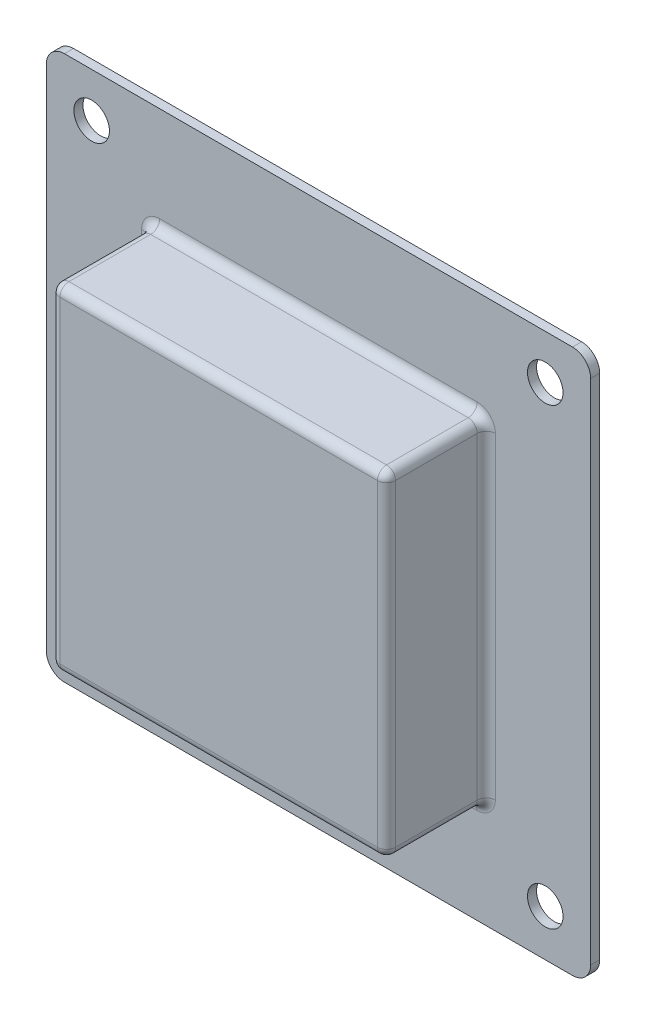
SolidWorks part; units mm, degrees
material "ABS PC"
ref_plane "Front Plane" through (0, 0, 0) normal (0, 0, 1) x (1, 0, 0)
ref_plane "Top Plane" through (0, 0, 0) normal (0, 1, 0) x (1, 0, 0)
ref_plane "Right Plane" through (0, 0, 0) normal (1, 0, 0) x (0, 0, -1)
sketch "Sketch1" plane through (0, 0, 0) normal (0, 0, 1) x (1, 0, 0)
  line L0 (34.9305, 50.2951) -> (34.9305, 88.3951)
  line L1 (34.9305, 85.8551) -> (34.9305, 14.7351) construction
  line L6 (34.9305, 88.3951) -> (-41.2695, 88.3951)
  line L7 (-41.2695, 88.3951) -> (-41.2695, 12.1951)
  line L8 (-41.2695, 12.1951) -> (34.9305, 12.1951)
  line L9 (34.9305, 12.1951) -> (34.9305, 50.2951)
  line L10 (34.9305, 50.2951) -> (19.0555, 50.2951) construction
  line L11 (19.0555, 50.2951) -> (19.0555, 72.5201)
  line L12 (19.0555, 72.5201) -> (-25.3945, 72.5201)
  line L13 (-25.3945, 72.5201) -> (-25.3945, 28.0701)
  line L14 (-25.3945, 28.0701) -> (19.0555, 28.0701)
  line L15 (19.0555, 28.0701) -> (19.0555, 50.2951)
extrude "Boss-Extrude1" add sketch "Sketch1" along normal blind 1.27
sketch "Sketch2" plane through (0, 0, 1.27) normal (0, 0, 1) x (1, 0, 0)
  line L0 (19.0555, 28.0701) -> (-25.3945, 28.0701)
  line L1 (-25.3945, 28.0701) -> (-25.3945, 72.5201)
  line L2 (-25.3945, 72.5201) -> (19.0555, 72.5201)
  line L3 (19.0555, 72.5201) -> (19.0555, 28.0701)
  line L4 (20.3255, 73.7901) -> (20.3255, 26.8001)
  line L5 (20.3255, 26.8001) -> (-26.6645, 26.8001)
  line L6 (-26.6645, 26.8001) -> (-26.6645, 73.7901)
  line L7 (-26.6645, 73.7901) -> (20.3255, 73.7901)
  dimension "D1" = 1.27
extrude "Boss-Extrude2" add sketch "Sketch2" along normal blind 12.7
sketch "Sketch3" plane through (0, 0, 13.97) normal (0, 0, 1) x (1, 0, 0)
  line L0 (20.3255, 26.8001) -> (-26.6645, 26.8001)
  line L1 (-26.6645, 26.8001) -> (-26.6645, 73.7901)
  line L2 (-26.6645, 73.7901) -> (20.3255, 73.7901)
  line L3 (20.3255, 73.7901) -> (20.3255, 26.8001)
extrude "Boss-Extrude3" add sketch "Sketch3" along normal blind 1.27
sketch "Sketch4" plane through (0, 26.8001, 0) normal (0, -1, 0) x (1, 0, 0)
  line L0 (-3.1695, 1.27) -> (-3.1695, 2.54) construction
  line L1 (-41.2695, 1.27) -> (34.9305, 1.27) construction
  line L2 (-3.1695, 2.54) -> (6.8, 2.54)
  line L3 (7.943, 3.683) -> (7.943, 3.937)
  line L4 (6.8, 5.08) -> (-13.139, 5.08)
  line L5 (-14.282, 3.937) -> (-14.282, 3.683)
  line L6 (-13.139, 2.54) -> (-3.1695, 2.54)
  arc A0 (7.943, 3.937) -> (6.8, 5.08) centre (6.8, 3.937) ccw
  arc A1 (6.8, 2.54) -> (7.943, 3.683) centre (6.8, 3.683) ccw
  arc A2 (-14.282, 3.683) -> (-13.139, 2.54) centre (-13.139, 3.683) ccw
  arc A3 (-13.139, 5.08) -> (-14.282, 3.937) centre (-13.139, 3.937) ccw
  point P11 (7.943, 5.08)
  point P14 (7.943, 2.54)
  point P17 (-14.282, 2.54)
  point P20 (-14.282, 5.08)
  dimension "D4" = 1.143
  dimension "D1" = 11.1125
  dimension "D2" = 22.225
  dimension "D3" = 2.54
extrude "Cut-Extrude1" cut sketch "Sketch4" against normal blind 1.27
hole_wizard "#10 Clearance Hole1" positions "Sketch5" profile "Sketch6" hole size "#10" standard "ANSI Inch" end condition through all
sketch "Sketch5" plane through (0, 0, 0) normal (0, 0, -1) x (-1, 0, 0)
  point P0 (-28.5805, 82.1818)
  point P3 (34.9195, 82.1818)
  point P6 (34.9195, 18.6818)
  point P9 (-28.5805, 18.6818)
sketch "Sketch6" plane through (28.5805, 82.1818, 0) normal (1, 0, 0) x (0, 1, 0)
  line L0 (0, 0) -> (0, 15.24)
  line L1 (0, 15.24) -> (2.4892, 15.24)
  line L2 (2.4892, 15.24) -> (2.4892, 0)
  line L5 (2.4892, 0) -> (0, 0)
  line L11 (0, -6.35) -> (0, 107.95) construction
  dimension "Thru Hole Dia." = 4.9784
  dimension "Thru Hole Depth" = 15.24
fillet "Fillet1" radius 2.54 4 edges at (-41.2695, 88.3951, 0.635) (34.9305, 88.3951, 0.635) (34.9305, 12.1951, 0.635) (-41.2695, 12.1951, 0.635)
fillet "Fillet2" radius 1.27 12 edges at (20.3255, 50.2951, 1.27) (20.3255, 73.7901, 8.255) (-3.1695, 73.7901, 15.24) (-3.1695, 73.7901, 1.27) (-26.6645, 73.7901, 8.255) (20.3255, 50.2951, 15.24) (-26.6645, 50.2951, 15.24) (-3.1695, 26.8001, 15.24) (20.3255, 26.8001, 8.255) (-26.6645, 26.8001, 8.255) (-3.1695, 26.8001, 1.27) (-26.6645, 50.2951, 1.27)
fillet "Fillet3" radius 0.635 8 edges at (19.0555, 28.0701, 6.985) (-25.3945, 28.0701, 6.985) (-3.1695, 28.0701, 13.97) (19.0555, 72.5201, 6.985) (19.0555, 50.2951, 13.97) (-25.3945, 50.2951, 13.97) (-3.1695, 72.5201, 13.97) (-25.3945, 72.5201, 6.985)
